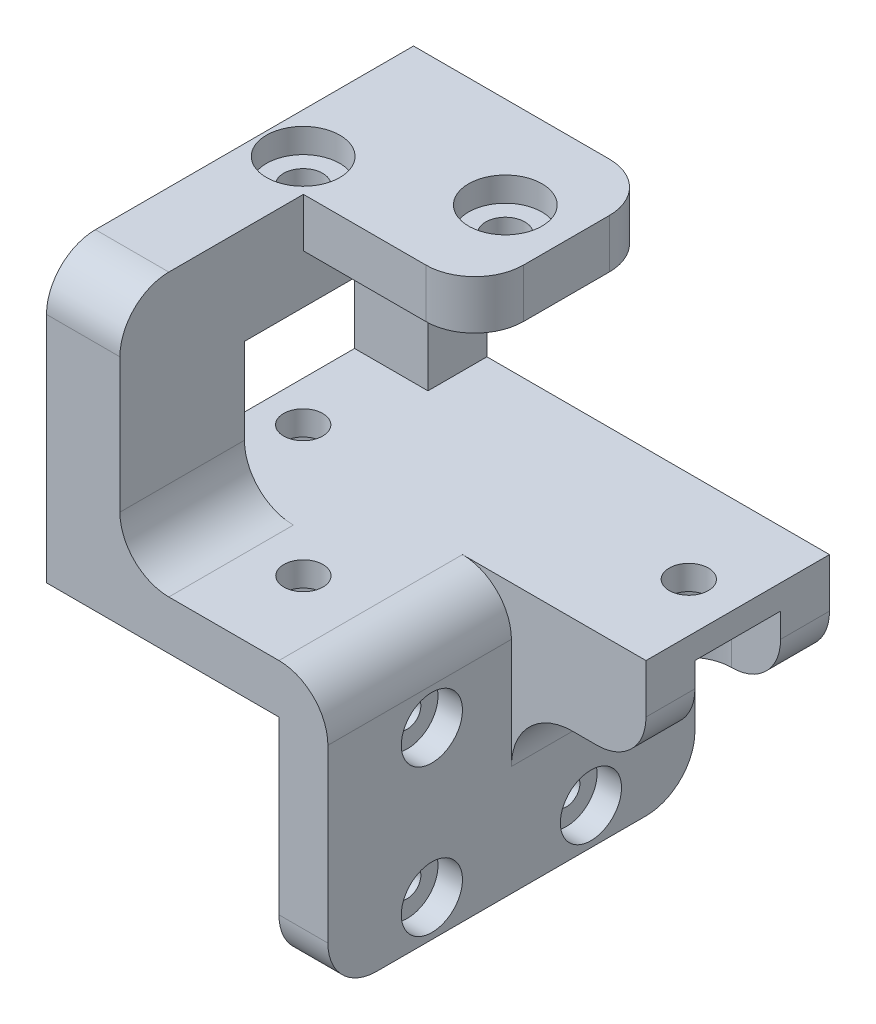
SolidWorks part; units mm, degrees
ref_plane "Plano frontal" through (0, 0, 0) normal (0, 0, 1) x (1, 0, 0)
ref_plane "Plano superior" through (0, 0, 0) normal (0, 1, 0) x (1, 0, 0)
ref_plane "Plano direito" through (0, 0, 0) normal (1, 0, 0) x (0, 0, -1)
sketch "Esboço1" plane through (0, 0, 0) normal (0, 0, 1) x (1, 0, 0)
  line L0 (0, 0) -> (4, 0)
  line L3 (15, 22) -> (-13, 22)
  line L4 (-13, 22) -> (-13, 37)
  line L5 (-13, 37) -> (1, 37)
  line L6 (1, 37) -> (1, 41)
  line L7 (1, 41) -> (-19, 41)
  line L9 (-19, 18) -> (0, 18)
  line L10 (0, 18) -> (0, 0)
  line L12 (15, 22) -> (15, 14)
  line L13 (4, 0) -> (4, 9)
  line L14 (15, 14) -> (31.662, 14) construction
  line L16 (-19, 18) -> (-19, 41)
  line L19 (9, 14) -> (15, 14)
  arc A0 (4, 9) -> (9, 14) centre (9, 9) cw
  dimension "D10" = 5
  dimension "D1" = 4
  dimension "D2" = 18
  dimension "D3" = 15
  dimension "D4" = 4
  dimension "D5" = 6
  dimension "D6" = 19
  dimension "D7" = 1
  dimension "D8" = 8
  dimension "D9" = 4
  dimension "D12" = 15
extrude "Ressalto-extrusão1" add sketch "Esboço1" along normal blind 30
sketch "Esboço3" plane through (0, 0, 0) normal (1, 0, 0) x (0, 0, -1)
  line L0 (0, 9) -> (-30, 9) construction
  line L1 (0, 18) -> (0, 0) construction
  line L2 (-30, 18) -> (-30, 0) construction
  line L4 (-30, 0) -> (0, 0) construction
  line L5 (-15, 0) -> (-15, 15) construction
  circle A0 centre (-8.5, 15) radius 1.1
  circle A4 centre (-21.5, 15) radius 1.1
  circle A5 centre (-8.5, 3) radius 1.1
  circle A6 centre (-21.5, 3) radius 1.1
  dimension "D3" = 2.2
  dimension "D1" = 12
  dimension "D2" = 13
extrude "Corte-extrusão1" cut sketch "Esboço3" against normal through all both and the other way through all
sketch "Esboço4" plane through (0, 0, 0) normal (0, 1, 0) x (1, 0, 0)
  line L0 (15, -15) -> (4, -15)
  line L1 (15, -30) -> (15, 0) construction
  line L2 (4, -30) -> (4, 0) construction
  line L3 (4, -15) -> (4, -30)
  line L4 (15, -15) -> (15, -30)
  line L5 (15, -30) -> (4, -30)
  line L6 (15, 0) -> (-13, 0) construction
  line L8 (4, -30) -> (4, -21.0417) construction
  dimension "D1" = 15
extrude "Corte-extrusão6" cut sketch "Esboço4" against normal through all and the other way through all
sketch "Esboço5" plane through (0, 41, 0) normal (0, 1, 0) x (1, 0, 0)
  line L0 (1, -30) -> (-19, -30) construction
  line L1 (15, -15) -> (15, 0) construction
  line L2 (15, -15) -> (15, 0) construction
  circle A0 centre (-5, -23) radius 1.6
  circle A1 centre (-15.7, -12.32) radius 1.6
  circle A2 centre (-5, -23) radius 4.84 construction
  circle A3 centre (-15.7, -12.32) radius 4.84 construction
  circle A4 centre (11, -7.5) radius 1.6
  point P15 (15, -7.5)
  dimension "D2" = 3.2
  dimension "D5" = 9.68
  dimension "D6" = 1
  dimension "D1" = 7
  dimension "D3" = 5
  dimension "D4" = 15.7
  dimension "D7" = 4
extrude "Corte-extrusão7" cut sketch "Esboço5" against normal through all
sketch "Esboço6" plane through (0, 22, 0) normal (0, 1, 0) x (1, 0, 0)
  line L0 (4, -15) -> (4, -30)
  line L1 (4, -30) -> (-13, -30)
  line L2 (-13, -30) -> (-13, -15)
  line L3 (-13, -30) -> (-13, 0) construction
  line L11 (-13, -15) -> (4, -15)
  circle A0 centre (-5, -23) radius 6.5 construction
  circle A1 centre (-15.7, -12.32) radius 7 construction
  dimension "D1" = 13
  dimension "D2" = 14
extrude "Corte-extrusão8" cut sketch "Esboço6" along normal blind 20
sketch "Esboço7" plane through (0, 22, 0) normal (0, 1, 0) x (1, 0, 0)
  line L1 (-23.2, -4.82) -> (-8.2, -4.82)
  line L2 (-23.2, -4.82) -> (-23.2, -19.82)
  line L3 (-23.2, -19.82) -> (-8.2, -19.82)
  line L4 (-8.2, -4.82) -> (-8.2, -19.82)
  circle A0 centre (-15.7, -12.32) radius 7.5 construction
  dimension "D1" = 15
extrude "Corte-extrusão9" cut sketch "Esboço7" along normal blind 11
sketch "Esboço9" plane through (0, 41, 0) normal (0, 1, 0) x (1, 0, 0)
  line L0 (1, -15) -> (1, 0) construction
  circle A1 centre (-4, -7.5) radius 1.6
  point P6 (1, -7.5)
  dimension "D1" = 3.2
  dimension "D3" = 5
extrude "Corte-extrusão11" cut sketch "Esboço9" against normal up to next
sketch "Esboço8" plane through (0, 41, 0) normal (0, 1, 0) x (1, 0, 0)
  circle A0 centre (-15.7, -12.32) radius 3
  circle A1 centre (-5, -23) radius 3
  circle A3 centre (-4, -7.5) radius 3
  circle A4 centre (-4, -7.5) radius 1.6 construction
  dimension "D1" = 6
extrude "Corte-extrusão10" cut sketch "Esboço8" against normal blind 2
sketch "Esboço11" plane through (15, 0, 0) normal (1, 0, 0) x (0, 0, -1)
  line L1 (-15, 22) -> (0, 22)
  line L2 (-15, 22) -> (-15, 0)
  line L3 (-15, 0) -> (0, 0)
  line L4 (0, 22) -> (0, 0)
  circle A0 centre (-8.5, 15) radius 2.5
  circle A1 centre (-8.5, 3) radius 2.5
  dimension "D1" = 5
extrude "Corte-extrusão12" cut sketch "Esboço11" against normal up to surface (11 mm away) contours A1 | A0 region at (15, 3, 8.5) up to face at (4, 3, 9.6)
sketch "Esboço12" plane through (4, 0, 0) normal (1, 0, 0) x (0, 0, -1)
  line L0 (-8.5, 15) -> (-8.5, 27.3693) construction
  line L2 (-12.25, 16.4) -> (-4.75, 16.4)
  line L3 (-12.25, 16.4) -> (-12.25, 22)
  line L4 (-12.25, 22) -> (-4.75, 22)
  line L5 (-4.75, 16.4) -> (-4.75, 22)
  line L6 (-12.25, 16.4) -> (-4.75, 22) construction
  line L7 (-12.25, 22) -> (-4.75, 16.4) construction
  line L8 (-30, 22) -> (-15, 22) construction
  point P3 (-8.5, 19.2)
  dimension "D1" = 7.5
  dimension "D2" = 5.6
extrude "Corte-extrusão13" [suppressed] cut sketch "Esboço12" against normal blind 6
sketch "Esboço14" plane through (0, 18, 0) normal (0, -1, 0) x (1, 0, 0)
  line L0 (11, 11) -> (15, 11)
  line L1 (-5, 26.2332) -> (-7.8, 24.6166)
  line L2 (-7.8, 24.6166) -> (-7.8, 21.3834)
  line L3 (-7.8, 21.3834) -> (-5, 19.7668)
  line L4 (-5, 19.7668) -> (-2.2, 21.3834)
  line L5 (-2.2, 21.3834) -> (-2.2, 24.6166)
  line L6 (-2.2, 24.6166) -> (-5, 26.2332)
  line L7 (-15.7, 15.5532) -> (-18.5, 13.9366)
  line L8 (-18.5, 13.9366) -> (-18.5, 10.7034)
  line L9 (-18.5, 10.7034) -> (-15.7, 9.0868)
  line L10 (-15.7, 9.0868) -> (-12.9, 10.7034)
  line L11 (-12.9, 10.7034) -> (-12.9, 13.9366)
  line L12 (-12.9, 13.9366) -> (-15.7, 15.5532)
  line L13 (15, 11) -> (15, 4)
  line L14 (15, 6.2087) -> (15, 0) construction
  line L15 (15, 4) -> (11, 4)
  circle A0 centre (-5, 23) radius 2.8 construction
  circle A1 centre (-15.7, 12.32) radius 2.8 construction
  arc A2 (11, 11) -> (11, 4) centre (11, 7.5) ccw
  dimension "D1" = 5.6
  dimension "D2" = 7
extrude "Corte-extrusão14" cut sketch "Esboço14" against normal blind 2 and the other way through all
sketch "Esboço15" plane through (4, 0, 0) normal (1, 0, 0) x (0, 0, -1)
  circle A0 centre (-21.5, 15) radius 2.5
  circle A1 centre (-8.5, 15) radius 2.5
  circle A2 centre (-8.5, 3) radius 2.5
  circle A3 centre (-21.5, 3) radius 2.5
  dimension "D1" = 5
extrude "Corte-extrusão16" cut sketch "Esboço15" against normal offset from surface 2 and the other way through all up to face at (0, 16.1, 21.5)
fillet "Filete1" radius 4 9 edges at (2, 0, 0) (2, 0, 30) (4, 22, 22.5) (1, 39, 0) (1, 39, 15) (-16, 41, 30) (-13, 22, 24.91) (15, 14, 2) (15, 14, 13)
